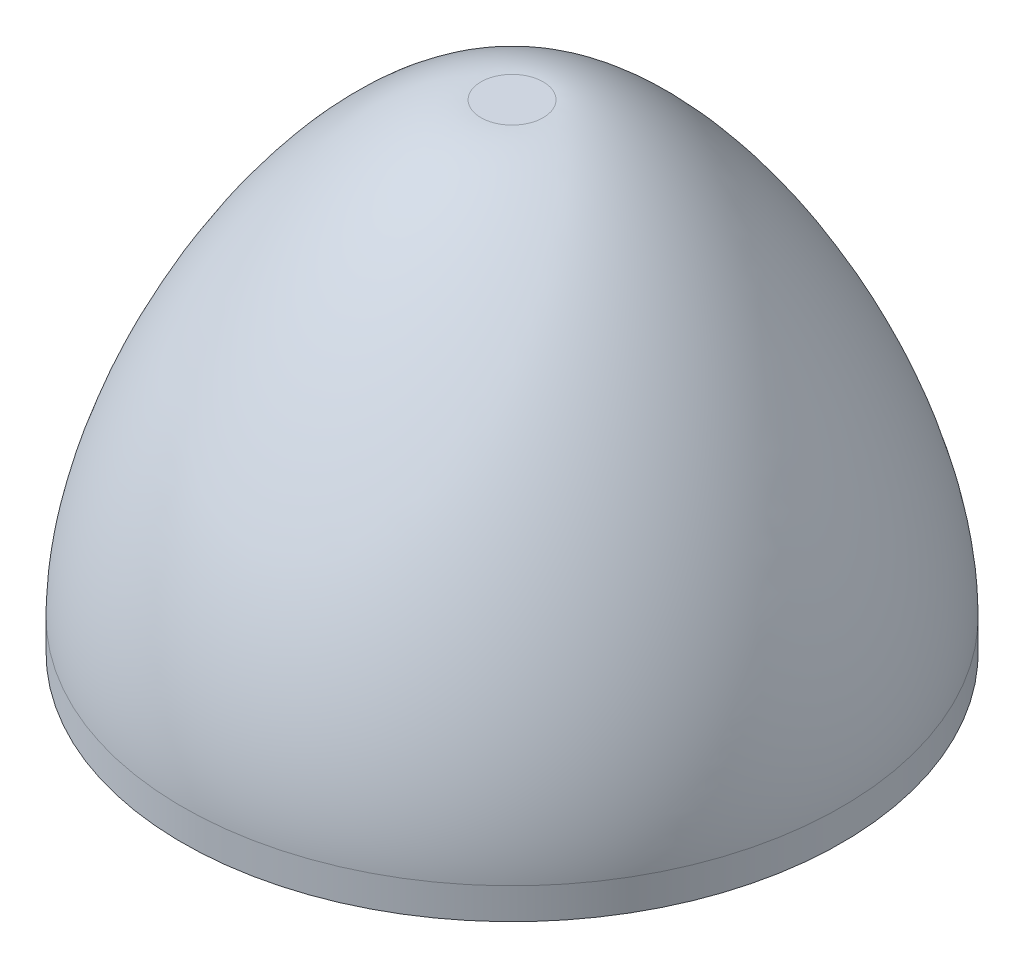
SolidWorks part; units mm, degrees
ref_plane "Front Plane" through (0, 0, 0) normal (0, 0, 1) x (1, 0, 0)
ref_plane "Top Plane" through (0, 0, 0) normal (0, 1, 0) x (1, 0, 0)
ref_plane "Right Plane" through (0, 0, 0) normal (1, 0, 0) x (0, 0, -1)
sketch "Sketch1" plane through (0, 0, 0) normal (0, 0, 1) x (1, 0, 0)
  line L1 (0, 62) -> (0, 0) construction
  line L5 (53, 0) -> (43, 0) construction
  line L6 (0, 62) -> (43, 62) construction
  line L7 (0, 0) -> (43, 0) construction
  line L13 (0, 72) -> (0, 62)
  line L14 (43, 0) -> (43, 62) construction
  line L19 (0, 72) -> (53, 72) construction
  line L20 (53, 72) -> (53, 0) construction
  line L21 (0, 72) -> (5, 72)
  line L22 (53, 0) -> (53, -5)
  line L23 (53, -5) -> (51, -5)
  line L25 (51, -5) -> (51, 0)
  line L27 (51, -5) -> (49, -5) construction
  line L28 (49, -5) -> (49, 0) construction
  line L29 (43, 0) -> (45, 0)
  line L30 (46.52, 0) -> (49, 0)
  line L31 (49, 0) -> (51, 0)
  arc A1 (46.52, 0) -> (45, 0) centre (45.76, 0) ccw
  conic Q0 (0, 62) -> (43, 0) control (43, 62) rho 0.3
  conic Q1 (5, 72) -> (53, 0) control (53, 72) rho 0.3
  dimension "o ring width" = 0.76
  dimension "Foam Thickness" = 10
  dimension "Egg Height/2" = 62
  dimension "egg max radius" = 43
  dimension "base radius" = 5
  dimension "outer thread width" = 2
  dimension "thread length" = 5
  dimension "inner thread width" = 2
  dimension "o ring inner radius" = 45
revolve "Revolve1" add sketch "Sketch1" angle 360 about L1
thread "Thread2" pitch 1 method extrude trim with end face yes profile "Thread Profile3" start angle 0, offset 0, length 0, pitch 1, diameter 102
ref_plane "Plane3" through (-51, 0, 0) normal (0, 0, 1) x (-1, 0, 0)
sketch "Thread Profile3" plane through (-51, 0, 0) normal (0, 0, 1) x (-1, 0, 0)
  line L0 (0, 0) -> (0, 1) construction
  line L11 (0, 0) -> (0, 0.875)
  line L12 (0, 0.875) -> (-0.5413, 0.5625)
  line L13 (-0.5413, 0.5625) -> (-0.5413, 0.3125)
  line L15 (-0.5413, 0.3125) -> (0, 0)
  line L17 (-0.5413, 0.4375) -> (0, 0.4375) construction
  point P2 (0, 0)
  dimension "Pitch" = 1
  dimension "Profile_Angle" = 60
  dimension "Profile_Land" = 0.25
  dimension "Profile_Height" = 0.5413
